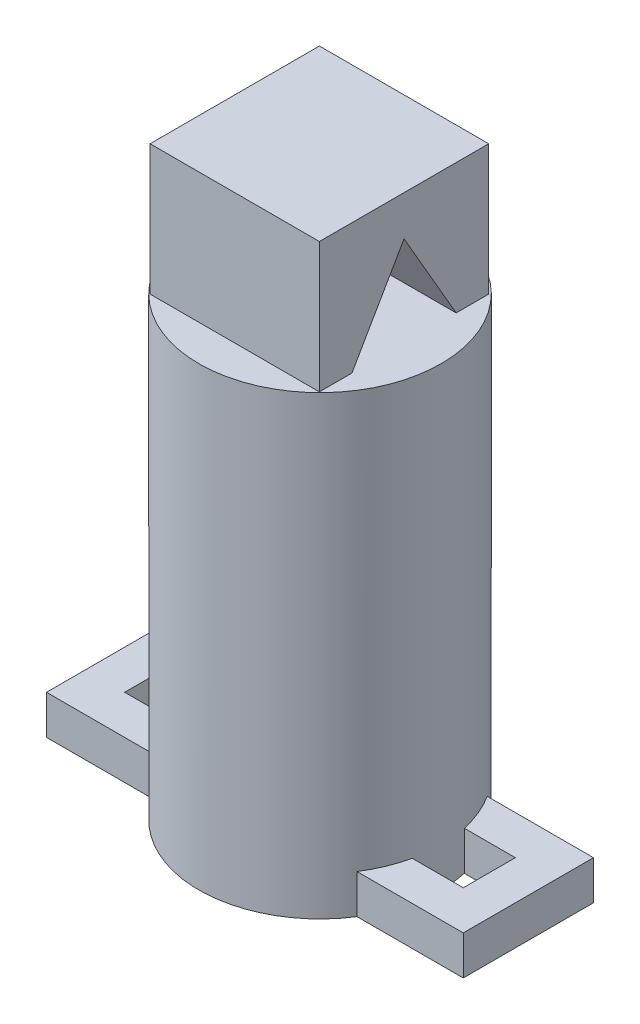
SolidWorks part; units mm, degrees
ref_plane "Front Plane" through (0, 0, 0) normal (0, 0, 1) x (1, 0, 0)
ref_plane "Top Plane" through (0, 0, 0) normal (0, 1, 0) x (1, 0, 0)
ref_plane "Right Plane" through (0, 0, 0) normal (1, 0, 0) x (0, 0, -1)
sketch "Sketch1" plane through (0, 0, 0) normal (0, 1, 0) x (1, 0, 0)
  line L1 (6.5, 6.4531) -> (-6.5, 6.4531)
  line L2 (6.5, 6.4531) -> (6.5, -6.5469)
  line L3 (6.5, -6.5469) -> (-6.5, -6.5469)
  line L4 (-6.5, 6.4531) -> (-6.5, -6.5469)
  line L5 (6.5, 6.4531) -> (-6.5, -6.5469) construction
  line L6 (6.5, -6.5469) -> (-6.5, 6.4531) construction
  dimension "D2" = 13
extrude "Boss-Extrude1" add sketch "Sketch1" along normal blind 10
sketch "Sketch2" plane through (0, 0, 0) normal (0, -1, 0) x (1, 0, 0)
  circle A0 centre (0, 0) radius 9.3
  dimension "D1" = 18.6
extrude "Boss-Extrude2" add sketch "Sketch2" along normal blind 35
sketch "Sketch3" plane through (0, -35, 0) normal (0, -1, 0) x (1, 0, 0)
  line L0 (-13, -2) -> (-13, -5) construction
  line L1 (-16, 5) -> (16, 5)
  line L2 (-16, 5) -> (-16, -5)
  line L3 (-16, -5) -> (16, -5)
  line L4 (16, 5) -> (16, -5)
  line L5 (-16, 5) -> (16, -5) construction
  line L6 (-16, -5) -> (16, 5) construction
  line L7 (-5.8, 2) -> (-13, 2)
  line L8 (-5.8, 2) -> (-5.8, -2)
  line L9 (-5.8, -2) -> (-13, -2)
  line L10 (-13, 2) -> (-13, -2)
  line L11 (-5.8, 2) -> (-13, -2) construction
  line L12 (-5.8, -2) -> (-13, 2) construction
  line L13 (-13, 2) -> (-13, 5) construction
  line L14 (0, -55) -> (0, 55) construction
  line L15 (5.8, 2) -> (13, -2) construction
  line L16 (5.8, -2) -> (13, 2) construction
  line L17 (5.8, 2) -> (5.8, -2)
  line L18 (5.8, -2) -> (13, -2)
  line L19 (5.8, 2) -> (13, 2)
  line L20 (13, 2) -> (13, -2)
  point P0 (0, 0)
  point P6 (-9.4, 0)
  point P19 (9.4, 0)
  point P20 (0, 0)
  point P21 (0, 0)
  point P22 (0, 0)
  point P23 (0, 0)
  dimension "D1" = 3
  dimension "D2" = 18.8
  dimension "D3" = 3
  dimension "D5" = 7.2
  dimension "D6" = 4
extrude "Boss-Extrude3" add sketch "Sketch3" against normal blind 3
sketch "Sketch4" plane through (-6.5, 0, 0) normal (-1, 0, 0) x (0, 0, 1)
  line L0 (-6.4531, 0) -> (6.5469, 0) construction
  line L1 (-3.9531, 0) -> (4.0469, 0)
  line L5 (-3.9531, 0) -> (-6.4531, 0) construction
  line L6 (6.5469, 0) -> (4.0469, 0) construction
  line L7 (-3.9531, 0) -> (0.0469, 6.9282)
  line L8 (0.0469, 6.9282) -> (4.0469, 0)
  point P1 (0, 7.1862)
  point P9 (0, 0)
  point P12 (0, 0)
  dimension "D1" = 120
  dimension "D2" = 8
extrude "Cut-Extrude1" cut sketch "Sketch4" against normal through all both and the other way through all
equation "\"D1@Sketch2\"=18.6"
equation "\"D1@Boss-Extrude2\"=42.8mm - 7.8mm"
